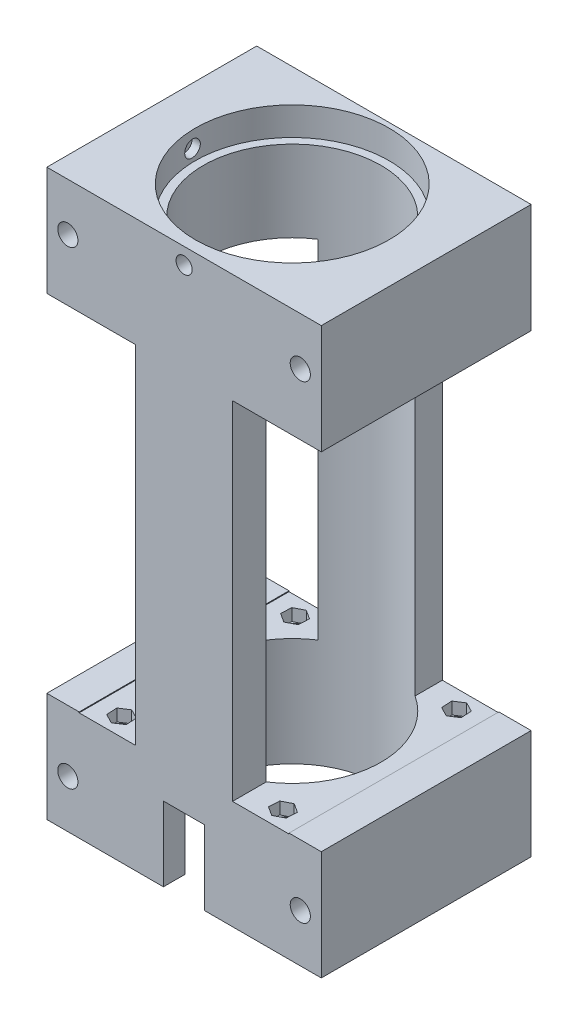
SolidWorks part; units mm, degrees
ref_plane "Front" through (0, 0, 0) normal (0, 0, 1) x (1, 0, 0)
ref_plane "Top" through (0, 0, 0) normal (0, 1, 0) x (1, 0, 0)
ref_plane "Right" through (0, 0, 0) normal (1, 0, 0) x (0, 0, -1)
sketch "草图1" plane through (0, 0, 0) normal (0, 0, 1) x (1, 0, 0)
  line L0 (-112, -70) -> (112, -70) construction
  line L1 (26, 70) -> (-26, 70)
  line L2 (26, 70) -> (26, -70)
  line L3 (26, -70) -> (-26, -70)
  line L4 (-26, 70) -> (-26, -70)
  line L5 (26, 70) -> (-26, -70) construction
  line L6 (26, -70) -> (-26, 70) construction
  point P0 (0, 0)
  dimension "D1" = 52
extrude "凸台-拉伸1" add sketch "草图1" along normal blind 52
sketch "草图2" plane through (0, 70, 0) normal (0, 1, 0) x (1, 0, 0)
  line L0 (26, 0) -> (-26, 0) construction
  circle A0 centre (0, -25.2) radius 22
  dimension "D1" = 44
  dimension "D2" = 25.2
extrude "切除-拉伸1" cut sketch "草图2" against normal through all contours A0
sketch "草图3" plane through (0, 0, 52) normal (0, 0, 1) x (1, 0, 0)
  line L1 (26, -70) -> (26, 70) construction
  line L3 (26, -43.1) -> (26, 42.9)
  line L4 (26, -43.1) -> (12, -43.1)
  line L5 (12, -43.1) -> (12, 42.9)
  line L6 (12, 42.9) -> (26, 42.9)
  line L7 (-26, -70) -> (26, -70) construction
  point P0 (19, -43.1)
  dimension "D1" = 86
  dimension "D2" = 26.9
  dimension "D3" = 14
extrude "切除-拉伸2" cut sketch "草图3" against normal up to surface (52 mm away)
mirror "镜向1" about plane through (0, 0, 0) normal (1, 0, 0) of "切除-拉伸2"
sketch "草图4" plane through (0, 70, 0) normal (0, 1, 0) x (1, 0, 0)
  circle A0 centre (0, -25.2) radius 24
  dimension "D1" = 48
extrude "切除-拉伸3" cut sketch "草图4" against normal blind 7
sketch "草图5" plane through (26, 0, 0) normal (1, 0, 0) x (0, 0, -1)
  line L0 (-52, 70) -> (0, 70) construction
  circle A0 centre (-26, 66) radius 2
  point P5 (-26, 70)
  dimension "D1" = 4
  dimension "D2" = 4
extrude "切除-拉伸4" cut sketch "草图5" against normal through all
sketch "草图6" plane through (0, 0, 52) normal (0, 0, 1) x (1, 0, 0)
  line L0 (26, 70) -> (-26, 70) construction
  circle A0 centre (0, 66) radius 2
  dimension "D1" = 4
  dimension "D2" = 4
extrude "切除-拉伸5" cut sketch "草图6" against normal blind 20
sketch "草图7" plane through (0, -43.1, 0) normal (0, 1, 0) x (1, 0, 0)
  line L0 (-12, -52) -> (-26, -52) construction
  line L1 (-22.3629, -46.2876) -> (-22.2314, -48.9402)
  line L2 (-22.2314, -48.9402) -> (-19.8685, -50.1526)
  line L3 (-19.8685, -50.1526) -> (-17.6371, -48.7124)
  line L4 (-17.6371, -48.7124) -> (-17.7686, -46.0598)
  line L5 (-17.7686, -46.0598) -> (-20.1315, -44.8474)
  line L6 (-20.1315, -44.8474) -> (-22.3629, -46.2876)
  line L7 (-26, 0) -> (-26, -52) construction
  circle A0 centre (-20, -47.5) radius 2.3 construction
  dimension "D1" = 4.6
  dimension "D2" = 4.5
  dimension "D3" = 6
extrude "切除-拉伸6" cut sketch "草图7" against normal blind 3
sketch "草图8" plane through (0, -46.1, 0) normal (0, 1, 0) x (1, 0, 0)
  line L0 (-26, 0) -> (-26, -52) construction
  line L1 (-12, -52) -> (-26, -52) construction
  circle A0 centre (-20, -47.5) radius 2.05
  dimension "D1" = 4.1
  dimension "D2" = 6
  dimension "D3" = 4.5
extrude "切除-拉伸7" cut sketch "草图8" against normal through all
mirror "镜向2" about plane through (0, 0, 0) normal (1, 0, 0) of "切除-拉伸6", "切除-拉伸7"
ref_plane "基准面2" through (0, 0, 26) normal (0, 0, 1) x (1, 0, 0)
mirror "镜向3" about plane through (0, 0, 26) normal (0, 0, 1) of "镜向2"
sketch "草图9" plane through (0, 0, 52) normal (0, 0, 1) x (1, 0, 0)
  line L0 (-26, 70) -> (-26, 42.9) construction
  line L1 (26, 42.9) -> (26, 70) construction
  line L2 (-26, 70) -> (-26, 42.9)
  line L3 (26, 42.9) -> (26, 70)
  line L4 (26, 42.9) -> (34, 42.9)
  line L5 (34, 42.9) -> (34, 70)
  line L6 (34, 70) -> (26, 70)
  line L7 (-26, 42.9) -> (-34, 42.9)
  line L8 (-34, 42.9) -> (-34, 70)
  line L9 (-34, 70) -> (-26, 70)
  dimension "D1" = 8
extrude "凸台-拉伸2" add sketch "草图9" against normal up to surface (52 mm away)
sketch "草图10" plane through (0, 0, 52) normal (0, 0, 1) x (1, 0, 0)
  line L0 (-34, 70) -> (-34, 42.9) construction
  line L1 (34, 42.9) -> (34, 70) construction
  circle A0 centre (28.8, 58.1086) radius 2.5
  circle A1 centre (-28.8, 58.1086) radius 2.5
  dimension "D1" = 5
  dimension "D2" = 5
  dimension "D3" = 5.2
  dimension "D4" = 5.2
extrude "切除-拉伸8" cut sketch "草图10" against normal through all
ref_plane "基准面3" through (0, 0, 0) normal (0, 1, 0) x (1, 0, 0)
mirror "镜向4" about plane through (0, 0, 0) normal (0, 1, 0) of "切除-拉伸8", "凸台-拉伸2"
sketch "草图11" plane through (0, 0, 52) normal (0, 0, 1) x (1, 0, 0)
  line L0 (-34, -70) -> (34, -70) construction
  line L1 (-5.1222, -70) -> (5, -70)
  line L2 (5, -70) -> (5, -51.5841)
  line L3 (5, -51.5841) -> (-5.1222, -51.5841)
  line L4 (-5.1222, -51.5841) -> (-5.1222, -70)
extrude "切除-拉伸9" cut sketch "草图11" against normal blind 10
